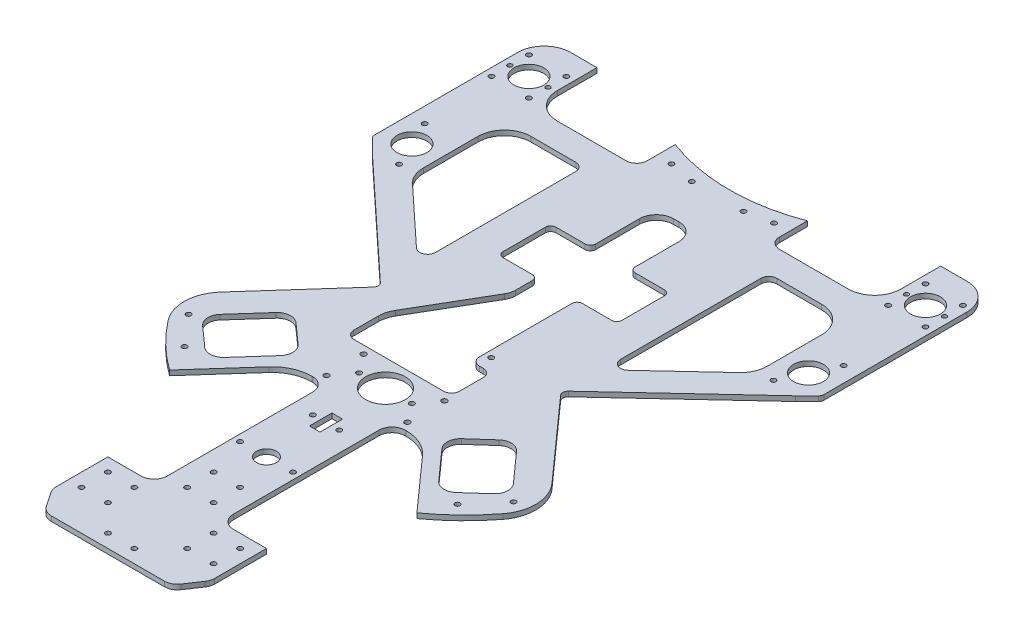
SolidWorks part; units mm, degrees
material "6063-T1"
ref_plane "Front Plane" through (0, 0, 0) normal (0, 0, 1) x (1, 0, 0)
ref_plane "Top Plane" through (0, 0, 0) normal (0, 1, 0) x (1, 0, 0)
ref_plane "Right Plane" through (0, 0, 0) normal (1, 0, 0) x (0, 0, -1)
sketch "Sketch1" plane through (0, 0, 0) normal (0, 1, 0) x (1, 0, 0)
  line L0 (-63.5, 31.75) -> (-178.5164, -97.0677)
  line L1 (-215.9, 31.75) -> (215.9, 31.75)
  line L2 (-215.9, 31.75) -> (-215.9, -31.75)
  line L3 (-215.9, -31.75) -> (215.9, -31.75)
  line L4 (215.9, 31.75) -> (215.9, -31.75)
  line L5 (-215.9, 31.75) -> (215.9, -31.75) construction
  line L6 (-215.9, -31.75) -> (215.9, 31.75) construction
  line L7 (63.5, 31.75) -> (-63.5, 31.75)
  line L8 (63.5, 31.75) -> (63.5, 292.608)
  line L9 (63.5, 292.608) -> (-63.5, 292.608)
  line L10 (-63.5, 31.75) -> (-63.5, 292.608)
  line L11 (0, -31.75) -> (-118.8264, -164.8348)
  line L12 (0, -31.75) -> (118.8264, -164.8348)
  line L13 (63.5, 31.75) -> (178.5164, -97.0677)
  line L14 (-62.3664, -101.6) -> (62.3664, -101.6)
  circle A1 centre (0, 0) radius 25.4 construction
  circle A2 centre (-25.4, 0) radius 2.3813
  circle A3 centre (25.4, 0) radius 2.3812
  circle A4 centre (0, 0) radius 203.2
  circle A5 centre (0, -76.2) radius 25.4 construction
  circle A6 centre (-25.4, -76.2) radius 2.3813
  circle A7 centre (25.4, -76.2) radius 2.3813
  point P0 (0, 0)
  dimension "D5" = 4.7625
  dimension "D6" = 4.7625
  dimension "D7" = 101.6
  dimension "D8" = 50.8
  dimension "D10" = 406.4
  dimension "D14" = 4.7625
  dimension "D15" = 4.7625
  dimension "D16" = 50.8
  dimension "D1" = 431.8
  dimension "D2" = 63.5
  dimension "D3" = 127
  dimension "D4" = 63.5
  dimension "D9" = 260.858
  dimension "D11" = 59.69
  dimension "D12" = 59.69
  dimension "D13" = 76.2
extrude "Boss-Extrude1" add sketch "Sketch1" along normal blind 4.7625 contours L10 L1 L8 L9 | L4 L1 L2 L3 A3 A2 | L0 A4 L11 L3 | L12 A4 L13 L3 | A4 L8 L9 L10 | L11 L14 L12 region at (0, 0, 3.2765) region at (0, 0, -115.8234) region at (-100.5416, 0, 84.5084) region at (0, 0, -246.176) region at (0, 0, 78.3341) region at (100.5416, 0, 84.5084)
sketch "Sketch2" plane through (0, 4.7625, 0) normal (0, 1, 0) x (1, 0, 0)
  line L0 (0, 292.608) -> (0, -101.6) construction
  line L1 (63.5, 292.608) -> (-63.5, 292.608) construction
  line L2 (-62.3664, -101.6) -> (62.3664, -101.6) construction
  circle A0 centre (25.4, 279.908) radius 2.3813
  circle A1 centre (50.8, 279.908) radius 2.3813
  circle A2 centre (-50.8, 279.908) radius 2.3813
  circle A3 centre (-25.4, 279.908) radius 2.3813
  dimension "D3" = 4.7625
  dimension "D4" = 4.7625
  dimension "D1" = 25.4
  dimension "D2" = 50.8
  dimension "D5" = 12.7
  dimension "D6" = 12.7
extrude "Cut-Extrude1" cut sketch "Sketch2" against normal through all
fillet "Fillet1" radius 38.1 4 edges at (63.5, 2.3813, -31.75) (-63.5, 2.3813, -31.75) (62.3664, 2.3813, 101.6) (-62.3664, 2.3813, 101.6)
sketch "Sketch4" plane through (0, 4.7625, 0) normal (0, 1, 0) x (1, 0, 0)
  line L0 (0, 292.608) -> (0, 0) construction
  line L1 (63.5, 292.608) -> (-63.5, 292.608) construction
  line L2 (0, 0) -> (0, -190.5) construction
  line L3 (0, 0) -> (-156.0485, -109.2663) construction
  circle A0 centre (0, 0) radius 190.5 construction
  circle A1 centre (-156.0485, -109.2663) radius 2.3813
  circle A2 centre (-131.1838, -138.1342) radius 2.3813
  circle A3 centre (131.1838, -138.1342) radius 2.3813
  circle A4 centre (156.0485, -109.2663) radius 2.3813
  dimension "D1" = 381
  dimension "D4" = 4.7625
  dimension "D5" = 4.7625
  dimension "D2" = 38.1
  dimension "D3" = 55
extrude "Cut-Extrude3" cut sketch "Sketch4" against normal through all
fillet "Fillet2" radius 38.1 2 edges at (178.5164, 2.3813, 97.0677) (-178.5164, 2.3813, 97.0677)
sketch "Sketch5" plane through (0, 4.7625, 0) normal (0, 1, 0) x (1, 0, 0)
  line L0 (-149.2765, -103.5959) -> (-111.3829, -137.4296)
  line L1 (-149.2765, -103.5959) -> (-106.9843, -56.229)
  line L2 (-111.3829, -137.4296) -> (-69.0908, -90.0627)
  line L3 (-106.9843, -56.229) -> (-69.0908, -90.0627)
  line L8 (-73.7278, -114.3247) -> (-118.8264, -164.8348) construction
  line L9 (0, 292.608) -> (0, -101.6) construction
  line L10 (63.5, 292.608) -> (-63.5, 292.608) construction
  line L11 (106.9843, -56.229) -> (69.0908, -90.0627)
  line L12 (111.3829, -137.4296) -> (69.0908, -90.0627)
  line L13 (149.2765, -103.5959) -> (106.9843, -56.229)
  line L14 (149.2765, -103.5959) -> (111.3829, -137.4296)
  line L15 (-45.3077, -101.6) -> (45.3077, -101.6) construction
  dimension "D1" = 50.8
  dimension "D2" = 12.7
  dimension "D3" = 63.5
  dimension "D4" = 25.4
extrude "Cut-Extrude4" cut sketch "Sketch5" against normal through all
fillet "Fillet3" radius 12.7 8 edges at (111.3829, 2.3813, 137.4296) (69.0908, 2.3813, 90.0627) (106.9843, 2.3813, 56.229) (149.2765, 2.3813, 103.5959) (-69.0908, 2.3813, 90.0627) (-106.9843, 2.3813, 56.229) (-149.2765, 2.3813, 103.5959) (-111.3829, 2.3813, 137.4296)
sketch "Sketch6" plane through (0, 4.7625, 0) normal (0, 1, 0) x (1, 0, 0)
  circle A0 centre (0, -76.2) radius 19.05
  dimension "D1" = 38.1
  dimension "D2" = 76.2
extrude "Cut-Extrude5" cut sketch "Sketch6" against normal through all
sketch "Sketch7" plane through (0, 4.7625, 0) normal (0, 1, 0) x (1, 0, 0)
  line L0 (-45.3077, -101.6) -> (45.3077, -101.6) construction
  line L1 (-19.05, 203.2) -> (19.05, 203.2)
  line L2 (-19.05, 203.2) -> (-19.05, -50.8)
  line L3 (-19.05, -50.8) -> (19.05, -50.8)
  line L4 (19.05, 203.2) -> (19.05, -50.8)
  line L5 (-19.05, 203.2) -> (19.05, -50.8) construction
  line L6 (-19.05, -50.8) -> (19.05, 203.2) construction
  point P0 (0, 76.2)
  dimension "D1" = 38.1
  dimension "D2" = 50.8
  dimension "D3" = 254
extrude "Cut-Extrude6" cut sketch "Sketch7" against normal through all
sketch "Sketch8" plane through (0, 4.7625, 0) normal (0, 1, 0) x (1, 0, 0)
  line L0 (-19.05, -50.8) -> (19.05, -50.8) construction
  line L1 (-63.5, -50.8) -> (38.1, -50.8)
  line L2 (-63.5, -50.8) -> (-63.5, -12.7)
  line L3 (-63.5, -12.7) -> (38.1, -12.7)
  line L4 (38.1, -50.8) -> (38.1, -12.7)
  dimension "D1" = 101.6
  dimension "D2" = 38.1
  dimension "D3" = 38.1
extrude "Cut-Extrude7" cut sketch "Sketch8" against normal through all
sketch "Sketch9" plane through (0, 4.7625, 0) normal (0, 1, 0) x (1, 0, 0)
  line L0 (-63.5, -12.7) -> (-19.05, 63.5)
  line L1 (-19.05, 203.2) -> (-19.05, -12.7) construction
  line L2 (-19.05, 63.5) -> (-19.05, -12.7)
  line L3 (-19.05, -12.7) -> (-63.5, -12.7)
  dimension "D1" = 76.2
extrude "Cut-Extrude8" cut sketch "Sketch9" against normal through all
fillet "Fillet4" radius 25.4 1 edges at (-63.5, 2.3813, 12.7)
fillet "Fillet5" radius 7.62 4 edges at (-63.5, 2.3813, 50.8) (38.1, 2.3813, 50.8) (38.1, 2.3813, 12.7) (19.05, 2.3813, 12.7)
fillet "Fillet8" radius 16.51 3 edges at (-19.05, 2.3813, -203.2) (19.05, 2.3813, -203.2) (-19.05, 2.3813, -63.5)
sketch "Sketch10" plane through (0, 4.7625, 0) normal (0, 1, 0) x (1, 0, 0)
  line L0 (0, 431.8) -> (0, 0) construction
  line L1 (0, 431.8) -> (-24.8652, 242.9298) construction
  line L2 (0, 431.8) -> (-49.305, 247.7911) construction
  circle A0 centre (0, 431.8) radius 177.8
  circle A1 centre (0, 431.8) radius 190.5 construction
  circle A2 centre (-49.305, 247.7911) radius 2.3812
  circle A3 centre (-24.8652, 242.9298) radius 2.3813
  circle A6 centre (24.8652, 242.9298) radius 2.3813
  circle A7 centre (49.305, 247.7911) radius 2.3812
  dimension "D1" = 355.6
  dimension "D3" = 381
  dimension "D4" = 4.7625
  dimension "D5" = 4.7625
  dimension "D6" = 7.5
  dimension "D7" = 15
  dimension "D2" = 431.8
extrude "Cut-Extrude9" cut sketch "Sketch10" against normal through all
sketch "Sketch11" plane through (0, 4.7625, 0) normal (0, 1, 0) x (1, 0, 0)
  line L1 (-215.9, 228.6) -> (215.9, 228.6)
  line L2 (-215.9, 228.6) -> (-215.9, 203.2)
  line L3 (-215.9, 203.2) -> (215.9, 203.2)
  line L4 (215.9, 228.6) -> (215.9, 203.2)
  line L5 (-215.9, 228.6) -> (215.9, 203.2) construction
  line L6 (-215.9, 203.2) -> (215.9, 228.6) construction
  point P0 (0, 215.9)
  dimension "D1" = 431.8
  dimension "D2" = 25.4
  dimension "D3" = 203.2
extrude "Boss-Extrude2" add sketch "Sketch11" against normal blind 4.7625
fillet "Fillet9" radius 10.16 4 edges at (63.5, 2.3813, -203.2) (63.5, 2.3813, -228.6) (-63.5, 2.3813, -203.2) (-63.5, 2.3813, -228.6)
sketch "Sketch12" plane through (0, 4.7625, 0) normal (0, 1, 0) x (1, 0, 0)
  line L0 (73.66, 203.2) -> (215.9, 203.2) construction
  line L1 (215.9, 203.2) -> (215.9, 228.6) construction
  line L2 (-215.9, 203.2) -> (-73.66, 203.2) construction
  line L3 (-215.9, 228.6) -> (-215.9, 203.2) construction
  circle A0 centre (-206.375, 215.9) radius 2.3813
  circle A1 centre (206.375, 215.9) radius 2.3813
  dimension "D1" = 4.7625
  dimension "D2" = 4.7625
  dimension "D3" = 12.7
  dimension "D4" = 9.525
  dimension "D5" = 12.7
  dimension "D6" = 9.525
extrude "Cut-Extrude10" cut sketch "Sketch12" against normal through all
sketch "Sketch13" plane through (0, 4.7625, 0) normal (0, 1, 0) x (1, 0, 0)
  line L0 (-45.3077, -101.6) -> (45.3077, -101.6) construction
  line L1 (-31.75, -101.6) -> (31.75, -101.6)
  line L2 (-31.75, -101.6) -> (-31.75, -266.7)
  line L3 (-31.75, -266.7) -> (31.75, -266.7)
  line L4 (31.75, -101.6) -> (31.75, -266.7)
  dimension "D1" = 63.5
  dimension "D2" = 31.75
  dimension "D3" = 165.1
extrude "Boss-Extrude3" add sketch "Sketch13" against normal up to surface (4.7625 mm away) up to face at (-206.375, 0, -213.5187)
fillet "Fillet10" radius 12.7 2 edges at (31.75, 2.3813, 101.6) (-31.75, 2.3813, 101.6)
sketch "Sketch14" plane through (0, 4.7625, 0) normal (0, 1, 0) x (1, 0, 0)
  circle A0 centre (-25.4, -190.5) radius 2.3813
  circle A1 centre (25.4, -190.5) radius 2.3813
  circle A2 centre (-25.4, -76.2) radius 2.3813 construction
  dimension "D1" = 4.7625
  dimension "D2" = 4.7625
  dimension "D3" = 114.3
  dimension "D4" = 25.4
  dimension "D5" = 25.4
extrude "Cut-Extrude11" cut sketch "Sketch14" against normal through all
sketch "Sketch15" plane through (0, 4.7625, 0) normal (0, 1, 0) x (1, 0, 0)
  line L0 (-31.75, -266.7) -> (31.75, -266.7) construction
  line L1 (-76.2, -266.7) -> (76.2, -266.7)
  line L2 (-76.2, -266.7) -> (-76.2, -342.9)
  line L3 (-76.2, -342.9) -> (76.2, -342.9)
  line L4 (76.2, -266.7) -> (76.2, -342.9)
  line L5 (-76.2, -266.7) -> (76.2, -342.9) construction
  line L6 (-76.2, -342.9) -> (76.2, -266.7) construction
  point P0 (0, -304.8)
  dimension "D1" = 76.2
  dimension "D2" = 152.4
extrude "Boss-Extrude4" add sketch "Sketch15" against normal up to surface (4.7625 mm away) up to face at (-25.4, 0, 192.8812)
fillet "Fillet11" radius 12.7 2 edges at (31.75, 2.3813, 266.7) (-31.75, 2.3813, 266.7)
sketch "Sketch16" plane through (0, 4.7625, 0) normal (0, 1, 0) x (1, 0, 0)
  line L1 (-5.08, -122.555) -> (5.08, -122.555)
  line L2 (-5.08, -122.555) -> (-5.08, -144.145)
  line L3 (-5.08, -144.145) -> (5.08, -144.145)
  line L4 (5.08, -122.555) -> (5.08, -144.145)
  line L5 (-5.08, -122.555) -> (5.08, -144.145) construction
  line L6 (-5.08, -144.145) -> (5.08, -122.555) construction
  point P0 (0, -133.35)
  dimension "D1" = 10.16
  dimension "D2" = 21.59
  dimension "D3" = 133.35
extrude "Cut-Extrude12" cut sketch "Sketch16" against normal through all
sketch "Sketch17" plane through (0, 4.7625, 0) normal (0, 1, 0) x (1, 0, 0)
  line L0 (-5.08, -144.145) -> (5.08, -144.145) construction
  line L2 (-5.08, -133.35) -> (5.08, -133.35) construction
  line L3 (-5.08, -122.555) -> (-5.08, -144.145) construction
  line L4 (5.08, -144.145) -> (5.08, -122.555) construction
  circle A0 centre (-12.7, -133.35) radius 2.3812
  circle A1 centre (12.7, -133.35) radius 2.3812
  point P6 (0, -144.145)
  dimension "D1" = 4.7625
  dimension "D2" = 4.7625
  dimension "D3" = 25.4
  dimension "D4" = 12.7
extrude "Cut-Extrude13" cut sketch "Sketch17" against normal through all
chamfer "Chamfer1" distance 15.24 angle 56 1 edges at (-76.2, 2.3813, 342.9) first distance on face at (0, 2.3813, 342.9)
chamfer "Chamfer2" distance 15.24 angle 56 1 edges at (76.2, 2.3813, 342.9) first distance on face at (7.62, 2.3813, 342.9)
fillet "Fillet13" radius 12.7 4 edges at (76.2, 2.3813, 320.3058) (60.96, 2.3813, 342.9) (-60.96, 2.3813, 342.9) (-76.2, 2.3813, 320.3058)
sketch "Sketch18" plane through (0, 4.7625, 0) normal (0, 1, 0) x (1, 0, 0)
  line L0 (0, -57.15) -> (0, -144.145) construction
  line L1 (-5.08, -144.145) -> (5.08, -144.145) construction
  line L2 (-27.7812, -76.2) -> (27.7812, -76.2) construction
  circle A0 centre (38.862, -93.98) radius 2.54
  circle A1 centre (0, -76.2) radius 19.05 construction
  circle A2 centre (25.4, -76.2) radius 2.3813 construction
  circle A3 centre (-38.862, -93.98) radius 2.54
  circle A4 centre (-25.4, -76.2) radius 2.3813 construction
  circle A5 centre (38.862, -58.42) radius 2.54
  circle A6 centre (-38.862, -58.42) radius 2.54
  dimension "D3" = 5.08
  dimension "D1" = 17.78
  dimension "D2" = 38.862
extrude "Cut-Extrude14" cut sketch "Sketch18" against normal through all
sketch "Sketch19" plane through (0, 4.7625, 0) normal (0, 1, 0) x (1, 0, 0)
  line L0 (-25.4, -190.5) -> (25.4, -190.5) construction
  line L1 (-31.75, -114.3) -> (-31.75, -254) construction
  circle A0 centre (0, -190.5) radius 9.525
  dimension "D1" = 19.05
  dimension "D2" = 31.75
extrude "Cut-Extrude15" cut sketch "Sketch19" against normal through all
sketch "Sketch20" plane through (0, 4.7625, 0) normal (0, 1, 0) x (1, 0, 0)
  line L0 (25.4, -317.5) -> (-25.4, -317.5) construction
  line L1 (25.4, -317.5) -> (25.4, -266.7) construction
  line L2 (25.4, -266.7) -> (-25.4, -266.7) construction
  line L3 (-25.4, -317.5) -> (-25.4, -266.7) construction
  line L4 (25.4, -317.5) -> (-25.4, -266.7) construction
  line L5 (25.4, -266.7) -> (-25.4, -317.5) construction
  line L6 (31.75, -254) -> (31.75, -114.3) construction
  line L7 (25.4, -317.5) -> (25.4, -266.7) construction
  line L11 (-54.2073, -342.9) -> (54.2073, -342.9) construction
  circle A8 centre (-63.5, -279.4) radius 2.3813
  circle A9 centre (-38.1, -279.4) radius 2.3813
  circle A10 centre (-63.5, -304.8) radius 2.3813
  circle A11 centre (-38.1, -304.8) radius 2.3813
  circle A16 centre (-12.7, -254) radius 2.3813
  circle A17 centre (12.7, -254) radius 2.3813
  circle A18 centre (12.7, -228.6) radius 2.3813
  circle A19 centre (-12.7, -228.6) radius 2.3813
  circle A20 centre (38.1, -279.4) radius 2.3813
  circle A21 centre (38.1, -304.8) radius 2.3813
  circle A22 centre (63.5, -304.8) radius 2.3813
  circle A23 centre (63.5, -279.4) radius 2.3813
  circle A24 centre (12.7, -330.2) radius 2.3813
  circle A25 centre (-12.7, -330.2) radius 2.3813
  circle A26 centre (-12.7, -355.6) radius 2.3813
  circle A27 centre (12.7, -355.6) radius 2.3813
  point P0 (0, -292.1)
  point P39 (0, -292.1)
  point P45 (0, -292.1)
  dimension "D4" = 25.4
  dimension "D6" = 4.7625
  dimension "D1" = 50.8
  dimension "D2" = 50.8
  dimension "D3" = 31.75
  dimension "D5" = 25.4
  dimension "D7" = 63.5
  dimension "D8" = 50.8
  dimension "D9" = 12.7
  dimension "D10" = 4
extrude "Cut-Extrude16" cut sketch "Sketch20" against normal through all
sketch "Sketch21" plane through (0, 4.7625, 0) normal (0, 1, 0) x (1, 0, 0)
  line L0 (-215.9, 228.6) -> (-215.9, 203.2) construction
  line L1 (-215.9, 292.1) -> (-165.1, 292.1)
  line L2 (-215.9, 292.1) -> (-215.9, 114.3)
  line L3 (-215.9, 114.3) -> (-165.1, 114.3)
  line L4 (-165.1, 292.1) -> (-165.1, 114.3)
  line L5 (-215.9, 292.1) -> (-165.1, 114.3) construction
  line L6 (-215.9, 114.3) -> (-165.1, 292.1) construction
  line L7 (0, 254) -> (0, 0) construction
  line L8 (215.9, 114.3) -> (165.1, 292.1) construction
  line L9 (215.9, 292.1) -> (165.1, 114.3) construction
  line L10 (165.1, 292.1) -> (165.1, 114.3)
  line L11 (215.9, 114.3) -> (165.1, 114.3)
  line L12 (215.9, 292.1) -> (215.9, 114.3)
  line L13 (215.9, 292.1) -> (165.1, 292.1)
  line L14 (-73.66, 228.6) -> (-215.9, 228.6) construction
  arc A0 (-63.5, 265.726) -> (63.5, 265.726) centre (0, 431.8) ccw construction
  point P0 (-190.5, 203.2)
  point P17 (190.5, 203.2)
  dimension "D1" = 50.8
  dimension "D2" = 177.8
  dimension "D3" = 63.5
extrude "Boss-Extrude5" add sketch "Sketch21" against normal up to surface (4.7625 mm away) up to face at (-63.5, 0, 307.1813)
sketch "Sketch22" plane through (0, 4.7625, 0) normal (0, 1, 0) x (1, 0, 0)
  line L0 (-215.9, 292.1) -> (-215.9, 114.3) construction
  line L1 (215.9, 114.3) -> (215.9, 292.1) construction
  line L3 (0, 254) -> (0, 0) construction
  line L4 (-165.1, 292.1) -> (-215.9, 292.1) construction
  circle A0 centre (-190.5, 252.095) radius 14.3256
  circle A1 centre (-190.5, 139.7) radius 14.3256
  circle A2 centre (190.5, 252.095) radius 14.3256
  circle A3 centre (190.5, 139.7) radius 14.3256
  circle A4 centre (-208.4605, 270.0555) radius 2.3813
  circle A5 centre (-172.5395, 270.0555) radius 2.3813
  circle A6 centre (-172.5395, 234.1345) radius 2.3813
  circle A7 centre (-208.4605, 234.1345) radius 2.3813
  arc A8 (-63.5, 265.726) -> (63.5, 265.726) centre (0, 431.8) ccw construction
  circle A9 centre (208.4605, 270.0555) radius 2.3812
  circle A10 centre (172.5395, 270.0555) radius 2.3812
  circle A11 centre (172.5395, 234.1345) radius 2.3813
  circle A12 centre (208.4605, 234.1345) radius 2.3813
  point P20 (-190.5, 252.095)
  dimension "D1" = 28.6512
  dimension "D2" = 28.6512
  dimension "D9" = 28.6512
  dimension "D10" = 28.6512
  dimension "D13" = 4.7625
  dimension "D3" = 112.395
  dimension "D4" = 112.395
  dimension "D5" = 25.4
  dimension "D6" = 25.4
  dimension "D7" = 40.005
  dimension "D8" = 25.4
  dimension "D11" = 25.4
  dimension "D12" = 25.4
  dimension "D14" = 4
extrude "Cut-Extrude17" cut sketch "Sketch22" against normal through all
fillet "Fillet14" radius 25.4 6 edges at (-165.1, 2.3813, -203.2) (165.1, 2.3813, -203.2) (165.1, 2.3813, -228.6) (-165.1, 2.3813, -228.6) (215.9, 2.3813, -292.1) (-215.9, 2.3812, -292.1)
sketch "Sketch23" plane through (0, 4.7625, 0) normal (0, 1, 0) x (1, 0, 0)
  line L0 (-203.2, 114.3) -> (-80.6901, 0.2345)
  line L2 (-165.1, 114.3) -> (-63.499, 19.7023)
  line L3 (0, 254) -> (0, 0) construction
  line L4 (-203.2, 114.3) -> (-165.1, 114.3)
  line L5 (-63.499, 19.7023) -> (-80.6901, 0.2345)
  line L6 (63.499, 19.7023) -> (80.6901, 0.2345)
  line L7 (203.2, 114.3) -> (165.1, 114.3)
  line L8 (165.1, 114.3) -> (63.499, 19.7023)
  line L9 (203.2, 114.3) -> (80.6901, 0.2345)
  line L10 (-215.9, 114.3) -> (-165.1, 114.3) construction
  arc A1 (-63.5, 265.726) -> (63.5, 265.726) centre (0, 431.8) ccw construction
  dimension "D1" = 38.1
extrude "Boss-Extrude7" add sketch "Sketch23" along direction (0, 1, 0) on the side against the normal blind 4.7625 contours L5 L2 L4 L0 | L9 L7 L8 L6 region at (-128.5522, 4.7625, -61.9828) region at (128.5522, 4.7625, -61.9828)
fillet "Fillet15" radius 25.4 2 edges at (165.1, 2.3813, -114.3) (-165.1, 2.3813, -114.3)
fillet "Fillet16" radius 5.08 4 edges at (69.69, 2.3813, -25.4665) (86.6688, 2.3813, -5.8011) (-86.6688, 2.3813, -5.8011) (-69.69, 2.3813, -25.4665)
chamfer "Chamfer3" distance 12.7 angle 45 2 edges at (215.9, 2.3813, -114.3) (-215.9, 2.3813, -114.3)
fillet "Fillet17" radius 5.08 2 edges at (215.9, 2.3813, -127) (-215.9, 2.3813, -127)
sketch "Sketch24" plane through (0, 4.7625, 0) normal (0, 1, 0) x (1, 0, 0)
  line L1 (-57.15, 139.7) -> (57.15, 139.7)
  line L2 (-57.15, 139.7) -> (-57.15, 88.9)
  line L3 (-57.15, 88.9) -> (57.15, 88.9)
  line L4 (57.15, 139.7) -> (57.15, 88.9)
  line L5 (-57.15, 139.7) -> (57.15, 88.9) construction
  line L6 (-57.15, 88.9) -> (57.15, 139.7) construction
  point P0 (0, 114.3)
  dimension "D1" = 114.3
  dimension "D2" = 50.8
  dimension "D3" = 57.15
  dimension "D4" = 114.3
extrude "Cut-Extrude18" cut sketch "Sketch24" against normal through all
fillet "Fillet18" radius 5.08 8 edges at (-19.05, 2.3812, -88.9) (19.05, 2.3812, -139.7) (19.05, 2.3812, -88.9) (57.15, 2.3812, -88.9) (57.15, 2.3812, -139.7) (-57.15, 2.3812, -88.9) (-57.15, 2.3812, -139.7) (-19.05, 2.3813, -139.7)
sketch "Sketch25" plane through (0, 4.7625, 0) normal (0, 1, 0) x (1, 0, 0)
  line L0 (-63.5, 46.2839) -> (-63.5, 193.04) construction
  line L1 (-88.9, 212.3464) -> (-63.5, 212.3464)
  line L2 (-88.9, 212.3464) -> (-88.9, 21.2795)
  line L3 (-88.9, 21.2795) -> (-63.5, 21.2795)
  line L4 (-63.5, 212.3464) -> (-63.5, 21.2795)
  line L5 (0, 254) -> (0, 0) construction
  line L6 (63.5, 212.3464) -> (63.5, 21.2795)
  line L7 (88.9, 21.2795) -> (63.5, 21.2795)
  line L8 (88.9, 212.3464) -> (88.9, 21.2795)
  line L9 (88.9, 212.3464) -> (63.5, 212.3464)
  arc A0 (-63.5, 265.726) -> (63.5, 265.726) centre (0, 431.8) ccw construction
  dimension "D1" = 25.4
extrude "Boss-Extrude8" add sketch "Sketch25" against normal up to surface (4.7625 mm away) up to face at (0, 0, 17.207)
fillet "Fillet19" radius 7.62 4 edges at (88.9, 2.3813, -43.3524) (-88.9, 2.3813, -43.3524) (88.9, 2.3813, -203.2) (-88.9, 2.3813, -203.2)
sketch "Sketch26" plane through (0, 4.7625, 0) normal (0, 1, 0) x (1, 0, 0)
  line L0 (-190.5, 165.1) -> (-190.5, 139.7) construction
  line L1 (-190.5, 139.7) -> (-201.2345, 162.7202) construction
  line L2 (0, 254) -> (0, 0) construction
  circle A0 centre (-190.5, 139.7) radius 25.4 construction
  circle A1 centre (-201.2345, 162.7202) radius 2.3813
  circle A2 centre (-179.7655, 116.6798) radius 2.3812
  arc A3 (-63.5, 265.726) -> (63.5, 265.726) centre (0, 431.8) ccw construction
  circle A4 centre (179.7655, 116.6798) radius 2.3812
  circle A5 centre (201.2345, 162.7202) radius 2.3813
  point P11 (-190.5, 139.7)
  dimension "D1" = 50.8
  dimension "D2" = 4.7625
  dimension "D3" = 25
  dimension "D4" = 2
extrude "Cut-Extrude19" cut sketch "Sketch26" against normal through all
sketch "Sketch27" plane through (0, 4.7625, 0) normal (0, 1, 0) x (1, 0, 0)
  line L0 (0, 254) -> (0, 0) construction
  line L1 (-172.212, 252.095) -> (-208.788, 252.095) construction
  circle A0 centre (-208.788, 252.095) radius 2.159
  circle A1 centre (-172.212, 252.095) radius 2.159
  circle A2 centre (-190.5, 252.095) radius 14.3256 construction
  arc A3 (-63.5, 265.726) -> (63.5, 265.726) centre (0, 431.8) ccw construction
  circle A4 centre (172.212, 252.095) radius 2.159
  circle A5 centre (208.788, 252.095) radius 2.159
  circle A6 centre (-190.5, 252.095) radius 14.3256
  point P18 (0, 0)
  dimension "D1" = 18.288
  dimension "D3" = 4.318
  dimension "D4" = 4.318
  dimension "D2" = 18.288
extrude "Cut-Extrude20" cut sketch "Sketch27" against normal through all
